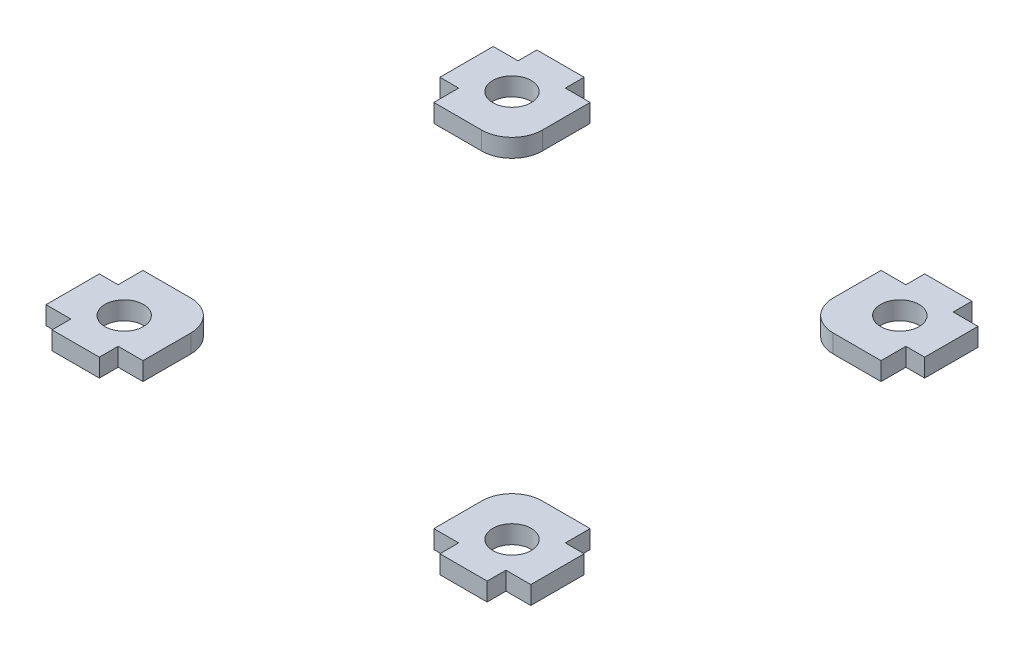
SolidWorks part; units mm, degrees
ref_plane "Front Plane" through (0, 0, 0) normal (0, 0, 1) x (1, 0, 0)
ref_plane "Top Plane" through (0, 0, 0) normal (0, 1, 0) x (1, 0, 0)
ref_plane "Right Plane" through (0, 0, 0) normal (1, 0, 0) x (0, 0, -1)
sketch "Sketch1" plane through (0, 0, 0) normal (0, 1, 0) x (1, 0, 0)
  line L0 (0, 40) -> (40, 40) construction
  line L1 (0, 0) -> (80, 0) construction
  line L2 (0, 0) -> (0, 80) construction
  line L3 (0, 80) -> (80, 80) construction
  line L4 (80, 0) -> (80, 80) construction
  line L5 (80, 0) -> (80, 80) construction
  line L6 (80, 80) -> (0, 80) construction
  line L7 (40, 40) -> (40, 80) construction
  line L8 (40, 40) -> (40, 80) construction
  line L9 (80, 40) -> (0, 40) construction
  line L10 (16, 16) -> (16, 0) construction
  line L11 (0, 0) -> (16, 0)
  line L12 (0, 0) -> (0, 16)
  line L13 (0, 16) -> (11, 16)
  line L14 (16, 0) -> (16, 11)
  line L15 (0, 16) -> (16, 16) construction
  line L16 (0, 0) -> (0, 80) construction
  line L17 (80, 0) -> (0, 0) construction
  line L18 (16, 80) -> (16, 69)
  line L19 (0, 64) -> (11, 64)
  line L20 (0, 80) -> (0, 64)
  line L21 (0, 80) -> (16, 80)
  line L22 (80, 80) -> (64, 80)
  line L23 (80, 80) -> (80, 64)
  line L24 (80, 64) -> (69, 64)
  line L25 (64, 80) -> (64, 69)
  line L26 (64, 0) -> (64, 11)
  line L27 (80, 16) -> (69, 16)
  line L28 (80, 0) -> (80, 16)
  line L29 (80, 0) -> (64, 0)
  circle A0 centre (8, 8) radius 3.175
  circle A1 centre (8, 8) radius 3.175 construction
  arc A2 (16, 69) -> (11, 64) centre (11, 69) cw
  circle A3 centre (8, 72) radius 3.175
  circle A4 centre (72, 72) radius 3.175
  arc A5 (16, 11) -> (11, 16) centre (11, 11) ccw
  arc A6 (64, 69) -> (69, 64) centre (69, 69) ccw
  arc A7 (64, 11) -> (69, 16) centre (69, 11) cw
  circle A8 centre (72, 8) radius 3.175
  point P49 (16, 16)
  dimension "D1" = 5
sketch "Sketch2" plane through (0, 0, 0) normal (0, 0, 1) x (1, 0, 0)
  line L0 (0, 0) -> (16, 0)
  line L1 (0, 0) -> (80, 0) construction
  line L2 (0, 0) -> (0, -3)
  line L3 (0, -3) -> (80, -3) construction
  line L4 (80, 0) -> (80, -3)
  line L5 (16, 0) -> (16, -3)
  line L6 (16, -3) -> (0, -3)
  line L7 (40, 0) -> (40, -3) construction
  line L8 (80, 0) -> (64, 0)
  line L9 (64, 0) -> (64, -3)
  line L10 (64, -3) -> (80, -3)
extrude "Boss-Extrude1" add sketch "Sketch1" against normal up to vertex (3 mm away) up to point (0, -3, 0)
sketch "Sketch3" plane through (0, 0, 0) normal (0, 1, 0) x (1, 0, 0)
  line L4 (16, 3) -> (12, 3)
  line L5 (12, 3) -> (12, 0)
  line L6 (12, 0) -> (16, 0)
  line L7 (16, 0) -> (16, 3)
  line L8 (16, 3) -> (12, 3) construction
  line L9 (12, 3) -> (12, 0) construction
  line L10 (12, 0) -> (16, 0) construction
  line L11 (16, 0) -> (16, 3) construction
  line L12 (3, 64) -> (3, 68)
  line L13 (3, 68) -> (0, 68)
  line L14 (0, 68) -> (0, 64)
  line L15 (0, 64) -> (3, 64)
  line L16 (3, 64) -> (3, 68) construction
  line L17 (3, 68) -> (0, 68) construction
  line L18 (0, 68) -> (0, 64) construction
  line L19 (0, 64) -> (3, 64) construction
  line L20 (80, 16) -> (77, 16)
  line L21 (80, 12) -> (80, 16)
  line L22 (77, 12) -> (80, 12)
  line L23 (77, 16) -> (77, 12)
  line L24 (80, 16) -> (77, 16) construction
  line L25 (80, 12) -> (80, 16) construction
  line L26 (77, 12) -> (80, 12) construction
  line L27 (77, 16) -> (77, 12) construction
  line L28 (80, 3) -> (76, 3)
  line L29 (80, 0) -> (80, 3)
  line L30 (76, 0) -> (80, 0)
  line L31 (76, 3) -> (76, 0)
  line L32 (80, 3) -> (76, 3) construction
  line L33 (80, 0) -> (80, 3) construction
  line L34 (76, 0) -> (80, 0) construction
  line L35 (76, 3) -> (76, 0) construction
  line L36 (4, 3) -> (0, 3)
  line L37 (4, 0) -> (4, 3)
  line L38 (0, 0) -> (4, 0)
  line L39 (0, 3) -> (0, 0)
  line L40 (4, 3) -> (0, 3) construction
  line L41 (4, 0) -> (4, 3) construction
  line L42 (0, 0) -> (4, 0) construction
  line L43 (0, 3) -> (0, 0) construction
  line L44 (0, 12) -> (3, 12)
  line L45 (0, 16) -> (0, 12)
  line L46 (3, 16) -> (0, 16)
  line L47 (3, 12) -> (3, 16)
  line L48 (0, 12) -> (3, 12) construction
  line L49 (0, 16) -> (0, 12) construction
  line L50 (3, 16) -> (0, 16) construction
  line L51 (3, 12) -> (3, 16) construction
  line L52 (68, 3) -> (64, 3)
  line L53 (68, 0) -> (68, 3)
  line L54 (64, 0) -> (68, 0)
  line L55 (64, 3) -> (64, 0)
  line L56 (68, 3) -> (64, 3) construction
  line L57 (68, 0) -> (68, 3) construction
  line L58 (64, 0) -> (68, 0) construction
  line L59 (64, 3) -> (64, 0) construction
  line L60 (76, 80) -> (76, 77)
  line L61 (80, 80) -> (76, 80)
  line L62 (80, 77) -> (80, 80)
  line L63 (76, 77) -> (80, 77)
  line L64 (76, 80) -> (76, 77) construction
  line L65 (80, 80) -> (76, 80) construction
  line L66 (80, 77) -> (80, 80) construction
  line L67 (76, 77) -> (80, 77) construction
  line L68 (64, 80) -> (64, 77)
  line L69 (68, 80) -> (64, 80)
  line L70 (68, 77) -> (68, 80)
  line L71 (64, 77) -> (68, 77)
  line L72 (64, 80) -> (64, 77) construction
  line L73 (68, 80) -> (64, 80) construction
  line L74 (68, 77) -> (68, 80) construction
  line L75 (64, 77) -> (68, 77) construction
  line L76 (16, 77) -> (16, 80)
  line L77 (16, 80) -> (12, 80)
  line L78 (12, 80) -> (12, 77)
  line L79 (12, 77) -> (16, 77)
  line L80 (16, 77) -> (16, 80) construction
  line L81 (16, 80) -> (12, 80) construction
  line L82 (12, 80) -> (12, 77) construction
  line L83 (12, 77) -> (16, 77) construction
  line L84 (4, 77) -> (4, 80)
  line L85 (4, 80) -> (0, 80)
  line L86 (0, 80) -> (0, 77)
  line L87 (0, 77) -> (4, 77)
  line L88 (4, 77) -> (4, 80) construction
  line L89 (4, 80) -> (0, 80) construction
  line L90 (0, 80) -> (0, 77) construction
  line L91 (0, 77) -> (4, 77) construction
  line L92 (80, 68) -> (77, 68)
  line L93 (77, 68) -> (77, 64)
  line L94 (77, 64) -> (80, 64)
  line L95 (80, 64) -> (80, 68)
  line L96 (80, 68) -> (77, 68) construction
  line L97 (77, 68) -> (77, 64) construction
  line L98 (77, 64) -> (80, 64) construction
  line L99 (80, 64) -> (80, 68) construction
  line L144 (16.1, 3.1) -> (11.9, 3.1)
  line L145 (11.9, 3.1) -> (11.9, -0.1)
  line L146 (11.9, -0.1) -> (16.1, -0.1)
  line L147 (16.1, -0.1) -> (16.1, 3.1)
  line L148 (3.1, 63.9) -> (3.1, 68.1)
  line L149 (3.1, 68.1) -> (-0.1, 68.1)
  line L150 (-0.1, 68.1) -> (-0.1, 63.9)
  line L151 (-0.1, 63.9) -> (3.1, 63.9)
  line L152 (80.1, 16.1) -> (76.9, 16.1)
  line L153 (76.9, 16.1) -> (76.9, 11.9)
  line L154 (76.9, 11.9) -> (80.1, 11.9)
  line L155 (80.1, 11.9) -> (80.1, 16.1)
  line L156 (80.1, 3.1) -> (75.9, 3.1)
  line L157 (75.9, 3.1) -> (75.9, -0.1)
  line L158 (75.9, -0.1) -> (80.1, -0.1)
  line L159 (80.1, -0.1) -> (80.1, 3.1)
  line L160 (4.1, 3.1) -> (-0.1, 3.1)
  line L161 (-0.1, 3.1) -> (-0.1, -0.1)
  line L162 (-0.1, -0.1) -> (4.1, -0.1)
  line L163 (4.1, -0.1) -> (4.1, 3.1)
  line L164 (-0.1, 11.9) -> (3.1, 11.9)
  line L165 (3.1, 11.9) -> (3.1, 16.1)
  line L166 (3.1, 16.1) -> (-0.1, 16.1)
  line L167 (-0.1, 16.1) -> (-0.1, 11.9)
  line L168 (68.1, 3.1) -> (63.9, 3.1)
  line L169 (63.9, 3.1) -> (63.9, -0.1)
  line L170 (63.9, -0.1) -> (68.1, -0.1)
  line L171 (68.1, -0.1) -> (68.1, 3.1)
  line L172 (75.9, 80.1) -> (75.9, 76.9)
  line L173 (75.9, 76.9) -> (80.1, 76.9)
  line L174 (80.1, 76.9) -> (80.1, 80.1)
  line L175 (80.1, 80.1) -> (75.9, 80.1)
  line L176 (63.9, 80.1) -> (63.9, 76.9)
  line L177 (63.9, 76.9) -> (68.1, 76.9)
  line L178 (68.1, 76.9) -> (68.1, 80.1)
  line L179 (68.1, 80.1) -> (63.9, 80.1)
  line L180 (16.1, 76.9) -> (16.1, 80.1)
  line L181 (16.1, 80.1) -> (11.9, 80.1)
  line L182 (11.9, 80.1) -> (11.9, 76.9)
  line L183 (11.9, 76.9) -> (16.1, 76.9)
  line L184 (4.1, 76.9) -> (4.1, 80.1)
  line L185 (4.1, 80.1) -> (-0.1, 80.1)
  line L186 (-0.1, 80.1) -> (-0.1, 76.9)
  line L187 (-0.1, 76.9) -> (4.1, 76.9)
  line L188 (80.1, 68.1) -> (76.9, 68.1)
  line L189 (76.9, 68.1) -> (76.9, 63.9)
  line L190 (76.9, 63.9) -> (80.1, 63.9)
  line L191 (80.1, 63.9) -> (80.1, 68.1)
  dimension "D1" = 0
  dimension "D2" = 0
  dimension "D3" = 0
  dimension "D4" = 0
  dimension "D5" = 0
  dimension "D6" = 0
  dimension "D7" = 0
  dimension "D8" = 0
  dimension "D9" = 0
  dimension "D10" = 0
  dimension "D11" = 0
  dimension "D12" = 0
  dimension "D13" = 0.1
extrude "Cut-Extrude1" cut sketch "Sketch3" against normal through all
